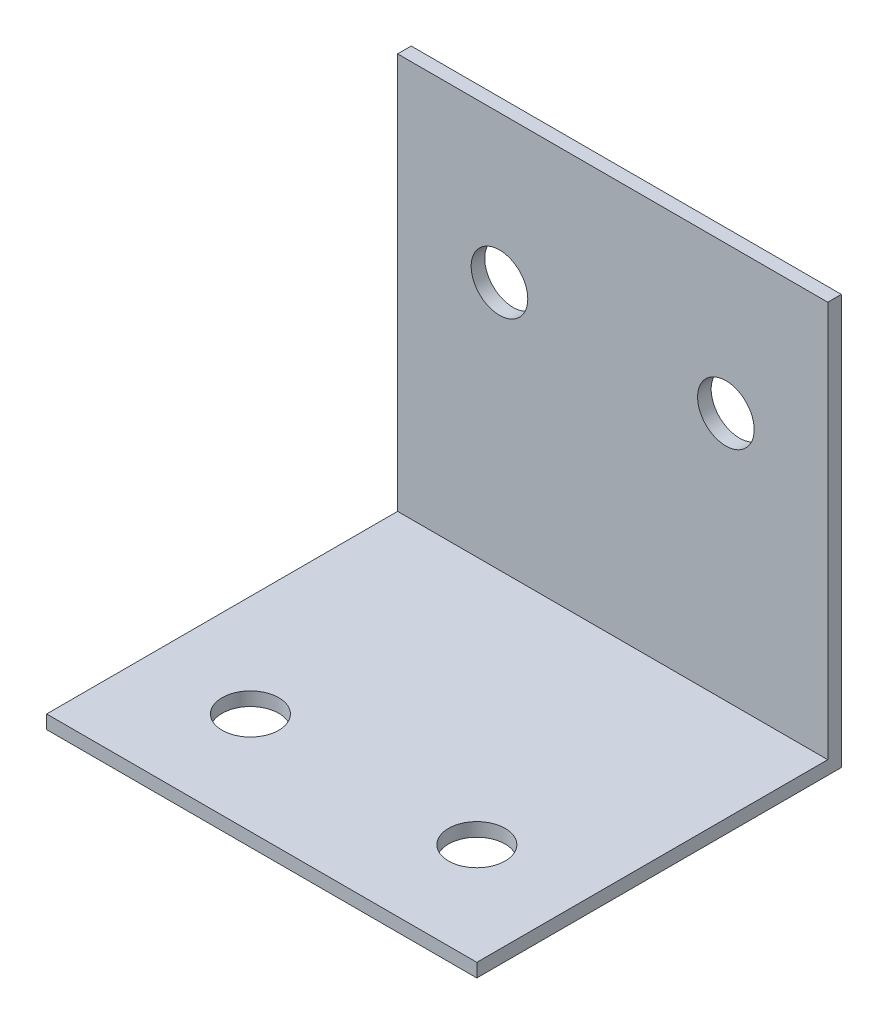
SolidWorks part; units mm, degrees
ref_plane "Front Plane" through (0, 0, 0) normal (0, 0, 1) x (1, 0, 0)
ref_plane "Top Plane" through (0, 0, 0) normal (0, 1, 0) x (1, 0, 0)
ref_plane "Right Plane" through (0, 0, 0) normal (1, 0, 0) x (0, 0, -1)
sketch "Sketch1" plane through (0, 0, 0) normal (0, 1, 0) x (1, 0, 0)
  line L0 (-19, 0) -> (-19, -32.2) construction
  line L1 (0, 0) -> (-38, 0)
  line L2 (0, 0) -> (0, -32.2)
  line L3 (0, -32.2) -> (-38, -32.2)
  line L4 (-38, 0) -> (-38, -32.2)
  circle A0 centre (-29, -23.2) radius 2.5
  circle A2 centre (-9, -23.2) radius 2.5
  dimension "D3" = 5
  dimension "D4" = 9
  dimension "D5" = 10
  dimension "D6" = 9
  dimension "D1" = 32.2
  dimension "D2" = 38
extrude "Boss-Extrude1" add sketch "Sketch1" along normal blind 1.2
sketch "Sketch2" plane through (0, 1.2, 0) normal (0, 1, 0) x (1, 0, 0)
  line L0 (0, -32.2) -> (0, 0) construction
  line L1 (-38, 0) -> (0, 0)
  line L2 (-38, 0) -> (-38, -1.2)
  line L3 (-38, -1.2) -> (0, -1.2)
  line L4 (0, 0) -> (0, -1.2)
  dimension "D1" = 1.2
extrude "Boss-Extrude2" add sketch "Sketch2" along normal blind 35
sketch "Sketch3" plane through (0, 0, 1.2) normal (0, 0, 1) x (1, 0, 0)
  line L0 (-19, 36.2) -> (-19, 1.2) construction
  line L1 (-38, 36.2) -> (0, 36.2) construction
  line L2 (-38, 1.2) -> (0, 1.2) construction
  line L5 (-38, 1.2) -> (0, 1.2) construction
  circle A4 centre (-29, 23.2) radius 2.5
  circle A5 centre (-9, 23.2) radius 2.5
  dimension "D1" = 5
  dimension "D2" = 22
  dimension "D3" = 10
extrude "Cut-Extrude1" cut sketch "Sketch3" against normal through all
